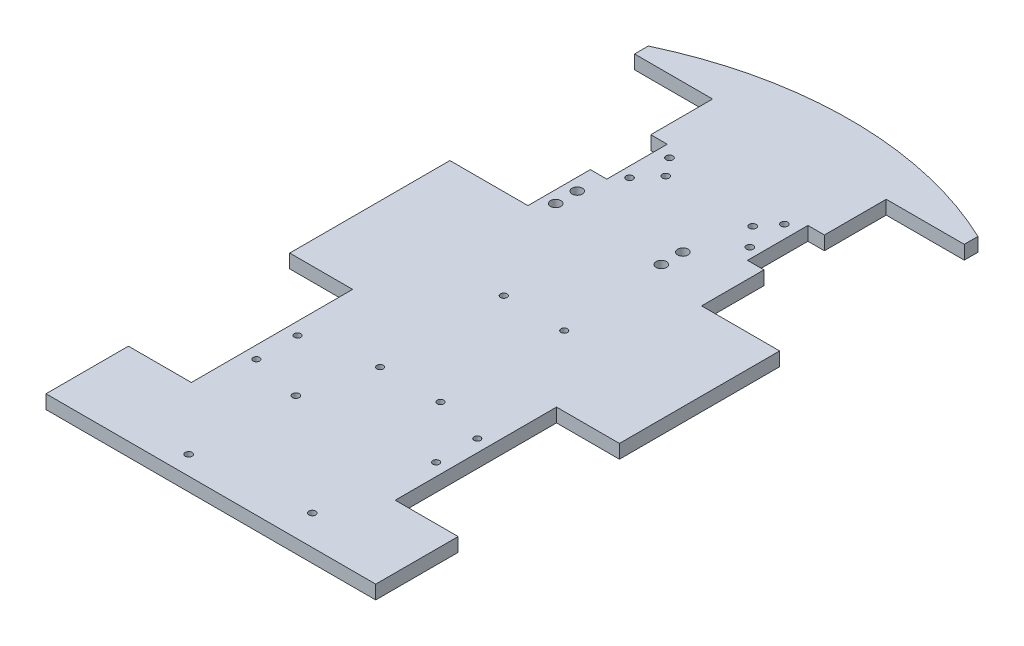
SolidWorks part; units mm, degrees
material "Oak"
ref_plane "Front Plane" through (0, 0, 0) normal (0, 0, 1) x (1, 0, 0)
ref_plane "Top Plane" through (0, 0, 0) normal (0, 1, 0) x (1, 0, 0)
ref_plane "Right Plane" through (0, 0, 0) normal (1, 0, 0) x (0, 0, -1)
sketch "Sketch1" plane through (0, 0, 0) normal (0, 1, 0) x (1, 0, 0)
  line L0 (50.292, 32.512) -> (76.2, 32.512) construction
  line L1 (0, 0) -> (0, -280.955) construction
  line L2 (0, 66.1738) -> (0, -229.362)
  line L3 (76.2, -229.362) -> (0, -229.362)
  line L7 (50.292, 32.512) -> (50.292, -32.512) construction
  line L8 (50.292, -32.512) -> (76.2, -32.512) construction
  line L9 (76.2, 32.512) -> (76.2, -32.512) construction
  line L10 (50.292, 32.512) -> (76.2, -32.512) construction
  line L11 (50.292, -32.512) -> (76.2, 32.512) construction
  line L18 (50.292, -119.888) -> (76.2, -119.888) construction
  line L19 (50.292, -119.888) -> (50.292, -184.912) construction
  line L20 (50.292, -184.912) -> (76.2, -184.912) construction
  line L21 (76.2, -119.888) -> (76.2, -184.912) construction
  line L22 (50.292, -119.888) -> (76.2, -184.912) construction
  line L23 (50.292, -184.912) -> (76.2, -119.888) construction
  line L25 (-76.2, 0) -> (76.2, 0) construction
  line L27 (-76.2, -152.4) -> (76.2, -152.4) construction
  line L28 (76.2, 0) -> (76.2, -152.4) construction
  line L33 (40.132, -42.672) -> (76.2, -42.672)
  line L34 (40.132, 42.672) -> (40.132, 14.097)
  line L35 (40.132, 42.672) -> (76.2, 42.672)
  line L36 (47.117, -191.262) -> (76.2, -191.262)
  line L37 (47.117, -116.713) -> (47.117, -191.262)
  line L38 (47.117, -116.713) -> (76.2, -116.713)
  line L43 (76.2, -42.672) -> (76.2, -116.713)
  line L45 (76.2, 42.672) -> (76.2, 49.022)
  line L47 (76.2, -191.262) -> (76.2, -229.362)
  line L55 (32.512, -13.843) -> (40.132, -13.843)
  line L56 (32.512, 14.097) -> (32.512, -13.843)
  line L57 (32.512, 14.097) -> (40.132, 14.097)
  line L58 (40.132, -13.843) -> (40.132, -42.672)
  arc A0 (0, 66.1738) -> (76.2, 49.022) centre (0, -111.6688) cw
  point P9 (63.246, 0)
  point P19 (63.246, -152.4)
  dimension "D7" = 3.175
  dimension "D8" = 6.35
  dimension "D12" = 7.62
  dimension "D16" = 6.35
  dimension "D1" = 152.4
  dimension "D2" = 152.4
  dimension "D3" = 126.492
  dimension "D4" = 25.908
  dimension "D6" = 3.175
  dimension "D9" = 10.16
  dimension "D10" = 10.16
  dimension "D5" = 65.024
  dimension "D11" = 10.16
  dimension "D13" = 27.94
  dimension "D14" = 28.575
  dimension "D15" = 38.1
extrude "Chassis" add sketch "Sketch1" along normal blind 6.35 contours L47 L36 L37 L38 L43 L33 L34 L55 L56 L57 L35 L45 region at (30.845, 0, 91.965)
mirror "Mirror1" about plane through (0, 6.35, 0) normal (1, 0, 0) of "Chassis"
sketch "Sketch2" plane through (0, 0, 0) normal (0, 1, 0) x (1, 0, 0)
  circle A0 centre (-26.5557, 9.17) radius 1.5875 construction
  circle A1 centre (-17.7031, -172.3599) radius 1.5875
  circle A2 centre (-17.7031, -172.3599) radius 1.5875
  circle A3 centre (-18.9731, -220.6199) radius 1.5875
  circle A4 centre (-18.9731, -220.6199) radius 1.5875
  circle A5 centre (33.0969, -215.5399) radius 1.5875
  circle A6 centre (33.0969, -215.5399) radius 1.5875
  circle A7 centre (-20.1056, 0.9994) radius 1.5875 construction
  circle A8 centre (-27.7865, -8.0406) radius 1.5875 construction
  circle A9 centre (26.5557, 9.17) radius 1.5875 construction
  circle A10 centre (20.1056, 0.9994) radius 1.5875 construction
  circle A11 centre (27.7865, -8.0406) radius 1.5875 construction
  circle A12 centre (14.2672, -25.46) radius 2.3813 construction
  circle A13 centre (14.2672, -35.4295) radius 2.3813 construction
  circle A14 centre (-34.5516, -25.46) radius 2.3813 construction
  circle A15 centre (-34.5516, -35.4295) radius 2.3813 construction
  circle A16 centre (18.288, -84.328) radius 1.5 construction
  circle A17 centre (-9.652, -84.328) radius 1.5 construction
  circle A18 centre (18.288, -141.478) radius 1.5 construction
  circle A19 centre (-9.652, -141.478) radius 1.5 construction
  circle A20 centre (-41.402, -147.875) radius 1.5 construction
  circle A21 centre (-41.402, -166.925) radius 1.5 construction
  circle A22 centre (41.402, -147.6053) radius 1.5 construction
  circle A23 centre (41.402, -166.6553) radius 1.5 construction
  circle A24 centre (-26.5557, 9.17) radius 1.5875
  circle A25 centre (-20.1056, 0.9994) radius 1.5875
  circle A26 centre (-27.7865, -8.0406) radius 1.5875
  circle A27 centre (26.5557, 9.17) radius 1.5875
  circle A28 centre (20.1056, 0.9994) radius 1.5875
  circle A29 centre (27.7865, -8.0406) radius 1.5875
  circle A30 centre (14.2672, -25.46) radius 2.3812
  circle A31 centre (14.2672, -35.4295) radius 2.3813
  circle A32 centre (-34.5516, -25.46) radius 2.3813
  circle A33 centre (-34.5516, -35.4295) radius 2.3812
  circle A34 centre (18.288, -84.328) radius 1.5
  circle A35 centre (-9.652, -84.328) radius 1.5
  circle A36 centre (18.288, -141.478) radius 1.5
  circle A37 centre (-9.652, -141.478) radius 1.5
  circle A38 centre (-41.402, -147.875) radius 1.5
  circle A39 centre (-41.402, -166.925) radius 1.5
  circle A40 centre (41.402, -147.6053) radius 1.5
  circle A41 centre (41.402, -166.6553) radius 1.5
  dimension "D1" = 0
  dimension "D2" = 0
  dimension "D3" = 0
extrude "Cut-Extrude1" cut sketch "Sketch2" along normal blind 17.78
